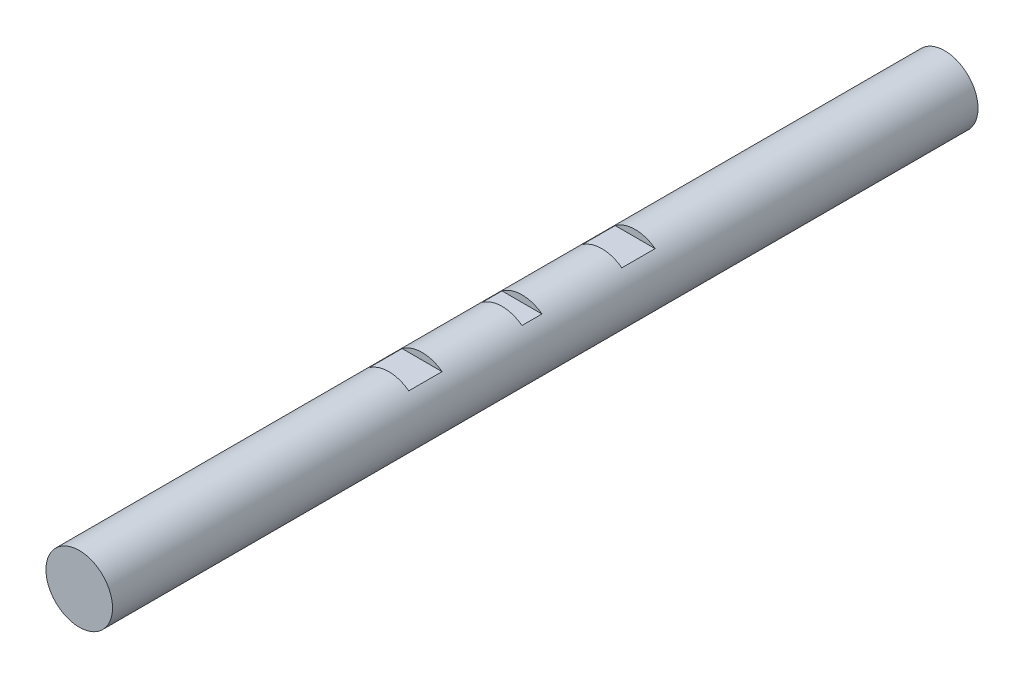
SolidWorks part; units mm, degrees
ref_plane "Front Plane" through (0, 0, 0) normal (0, 0, 1) x (1, 0, 0)
ref_plane "Top Plane" through (0, 0, 0) normal (0, 1, 0) x (1, 0, 0)
ref_plane "Right Plane" through (0, 0, 0) normal (1, 0, 0) x (0, 0, -1)
sketch "Sketch1" plane through (0, 0, 0) normal (0, 0, 1) x (1, 0, 0)
  circle A0 centre (0, 0) radius 5
extrude "Boss-Extrude1" add sketch "Sketch1" along normal blind 65 and the other way blind 65
sketch "Sketch3" plane through (0, 0, 0) normal (1, 0, 0) x (0, 0, -1)
  line L0 (65, 5) -> (-65, 5) construction
  line L1 (18.5, 5) -> (13.5, 5)
  line L2 (18.5, 5) -> (18.5, 4)
  line L3 (18.5, 4) -> (13.5, 4)
  line L4 (13.5, 5) -> (13.5, 4)
  line L6 (-13.5, 5) -> (-18.5, 5)
  line L7 (-13.5, 5) -> (-13.5, 4)
  line L8 (-13.5, 4) -> (-18.5, 4)
  line L9 (-18.5, 5) -> (-18.5, 4)
  line L11 (1.5, 5) -> (-1.5, 5)
  line L12 (1.5, 5) -> (1.5, 4)
  line L13 (1.5, 4) -> (-1.5, 4)
  line L14 (-1.5, 5) -> (-1.5, 4)
  line L15 (65, 5) -> (-65, 5) construction
  point P6 (-0.8949, 4)
  point P7 (-0.2991, 4)
  point P8 (0, 4)
  dimension "D1" = 5
  dimension "D2" = 1
  dimension "D3" = 37
  dimension "D5" = 3
  dimension "D6" = 12
extrude "Cut-Extrude1" cut sketch "Sketch3" against normal through all both and the other way through all
